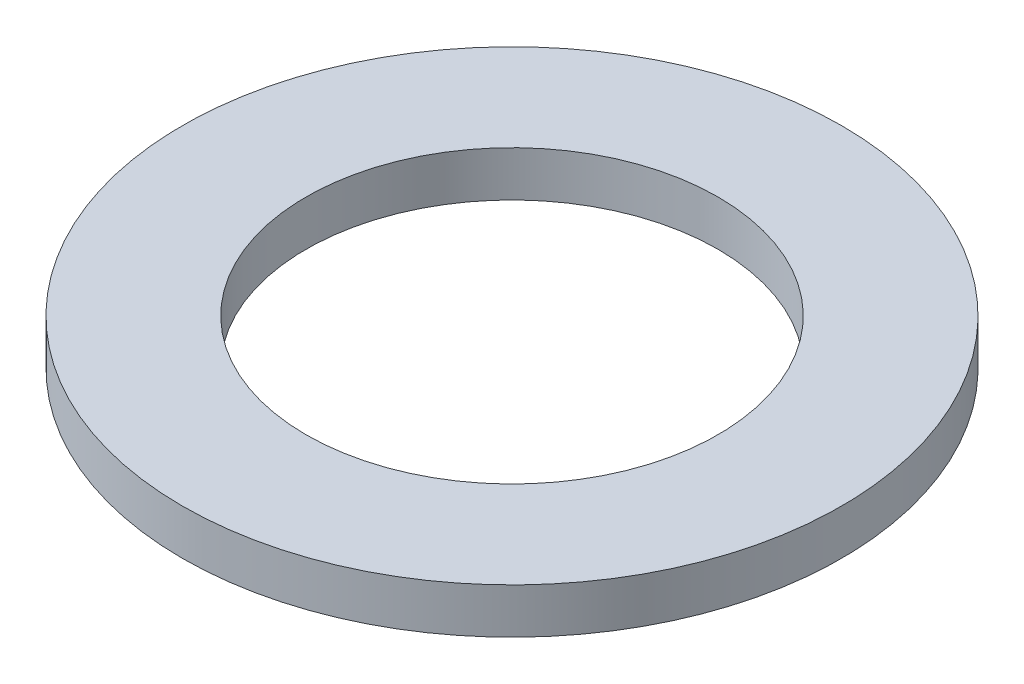
SolidWorks part; units mm, degrees
ref_plane "Front Plane" through (0, 0, 0) normal (0, 0, 1) x (1, 0, 0)
ref_plane "Top Plane" through (0, 0, 0) normal (0, 1, 0) x (1, 0, 0)
ref_plane "Right Plane" through (0, 0, 0) normal (1, 0, 0) x (0, 0, -1)
sketch "Sketch1" plane through (0, 0, 0) normal (0, 1, 0) x (1, 0, 0)
  circle A0 centre (0, 0) radius 80
  dimension "FLANGE_OD" = 160
extrude "Boss-Extrude1" add sketch "Sketch1" along normal blind 11
sketch "Sketch2" plane through (0, 0, 0) normal (0, 1, 0) x (1, 0, 0)
  circle A0 centre (0, 0) radius 50
  dimension "BORE_D" = 100
extrude "Cut-Extrude1" cut sketch "Sketch2" along normal through all
sketch "Sketch3" plane through (0, 11, 0) normal (0, 1, 0) x (1, 0, 0)
  circle A0 centre (0, 0) radius 32.695 construction
  circle A1 centre (-32.695, 0) radius 3.4832
  dimension "BOLT_D" = 6.9664
  dimension "BOLT_PCD" = 65.3899
extrude "Cut-Extrude2" cut sketch "Sketch3" against normal blind 10.77 rebuild error yes
pattern_circular "CirPattern1" count 8 over 360 rebuild error yes
